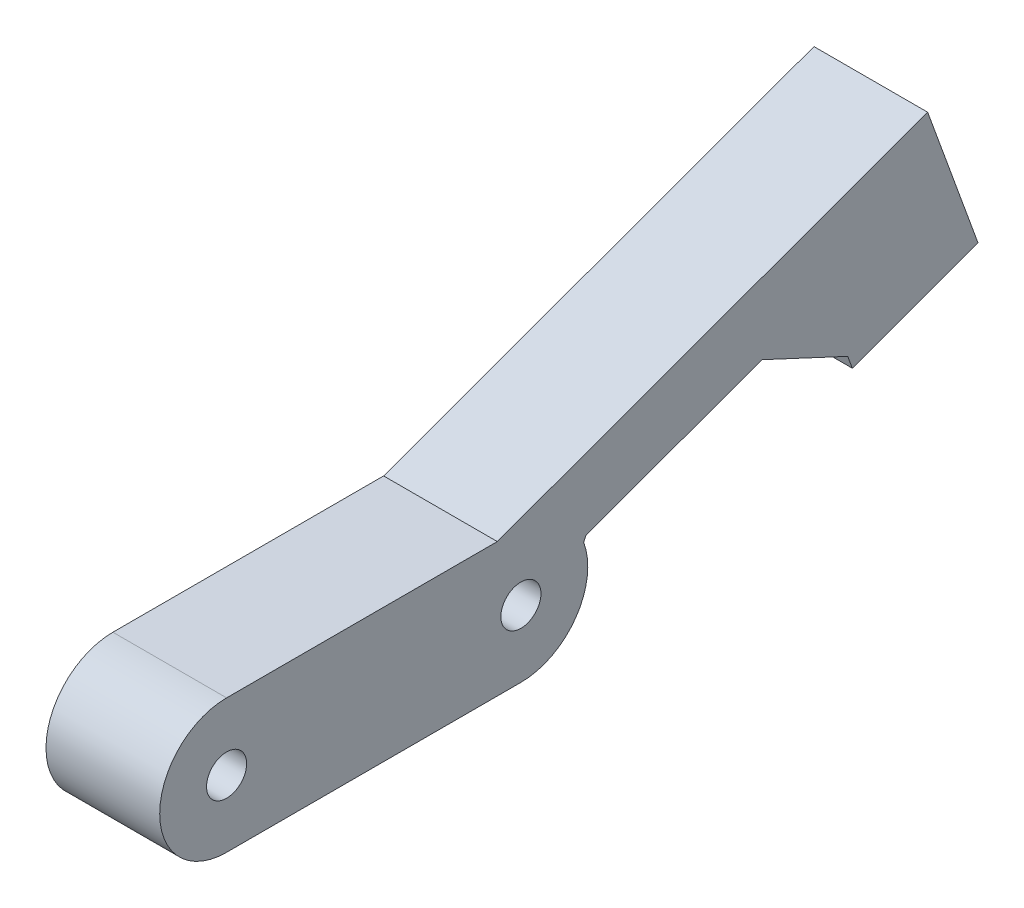
SolidWorks part; units mm, degrees
ref_plane "Front Plane" through (0, 0, 0) normal (0, 0, 1) x (1, 0, 0)
ref_plane "Top Plane" through (0, 0, 0) normal (0, 1, 0) x (1, 0, 0)
ref_plane "Right Plane" through (0, 0, 0) normal (1, 0, 0) x (0, 0, -1)
sketch "Sketch1" plane through (0, 0, 0) normal (1, 0, 0) x (0, 0, -1)
  line L1 (0, 0) -> (27, 0)
  line L2 (0, 0) -> (0, 10)
  line L3 (0, 10) -> (27, 10)
  circle A0 centre (5, 5) radius 1.5
  circle A1 centre (5, 5) radius 5
  circle A2 centre (27, 5) radius 5
  circle A3 centre (27, 5) radius 1.5
  dimension "D7" = 3
  dimension "D11" = 10
  dimension "D2" = 3
  dimension "D1" = 10
  dimension "D8" = 5
  dimension "D9" = 5
  dimension "D10" = 22
extrude "Boss-Extrude1" add sketch "Sketch1" along normal blind 8.5 contours A1 A0 | A2 L3 A1 L1 | A2 A3 | L2 A1 | L1 A1 region at (0, 5, -16) region at (0, 1.5645, -1.5645) region at (0, 5, -22.1414)
sketch "Sketch2" plane through (8.5, 0, 0) normal (1, 0, 0) x (0, 0, -1)
  line L0 (27, 0) -> (60.8289, 12.3127)
  line L1 (5, 0) -> (27, 0) construction
  line L3 (60.8289, 12.3127) -> (57.4087, 21.7097)
  line L5 (57.4087, 21.7097) -> (25.2367, 10)
  line L6 (5, 10) -> (27, 10) construction
  line L7 (31.8677, 7.0926) -> (45.0234, 11.8809)
  line L8 (31.8677, 7.0926) -> (28.8794, 0.684)
  line L9 (45.0234, 11.8809) -> (51.432, 8.8925)
  line L10 (51.432, 8.8925) -> (60.8289, 12.3127)
  line L11 (51.432, 8.8925) -> (51.774, 7.9528)
  line L12 (60.8289, 12.3127) -> (61.171, 11.373)
  line L13 (51.774, 7.9528) -> (61.171, 11.373)
  line L14 (5, 10) -> (27, 10)
  arc A3 (27, 0) -> (27, 10) centre (27, 5) ccw construction
  arc A4 (27, 0) -> (27, 10) centre (27, 5) ccw
  line M1 (27, 10) -> (5, 10)
  arc M4 (27, 0) -> (27, 10) centre (27, 5) ccw
  dimension "D1" = 160
  dimension "D2" = 36
  dimension "D3" = 90
  dimension "D4" = 10
  dimension "D5" = 10
  dimension "D6" = 45
  dimension "D7" = 45
  dimension "D8" = 5
  dimension "D9" = 5
  dimension "D10" = 14
  dimension "D11" = 1
extrude "Boss-Extrude2" add sketch "Sketch2" against normal blind 8.5 contours L7 L9 L0 L3 L5 L8 M1 M4 | L11 L13 L12 L0 region at (8.5, 13.7272, -46.7622) region at (8.5, 10.1328, -56.3015)
sketch "Sketch3" plane through (8.5, 0, 0) normal (1, 0, 0) x (0, 0, -1)
  line L0 (51.432, 8.8925) -> (27, 0)
  line L1 (5, 0) -> (27, 0) construction
  circle A0 centre (27, 5) radius 5
  arc M4 (27, 0) -> (31.6945, 6.721) centre (27, 5) ccw
  dimension "D1" = 160
extrude "Cut-Extrude1" [suppressed] cut sketch "Sketch3" against normal blind 3 contours L0 M4
sketch "Sketch4" plane through (8.5, 0, 0) normal (1, 0, 0) x (0, 0, -1)
  line L0 (52.2404, 19.8285) -> (59.2898, 16.5413)
  line L1 (57.4087, 21.7097) -> (25.2367, 10) construction
  line L2 (61.171, 11.373) -> (57.4087, 21.7097) construction
  line L3 (45.0234, 11.8809) -> (51.432, 8.8925) construction
  line L4 (57.4087, 21.7097) -> (25.2367, 10)
  line L5 (61.171, 11.373) -> (57.4087, 21.7097)
  line M8 (61.171, 11.373) -> (57.4087, 21.7097)
  line M9 (57.4087, 21.7097) -> (25.2367, 10)
extrude "Cut-Extrude2" [suppressed] cut sketch "Sketch4" against normal through all contours L0 M9 M8
